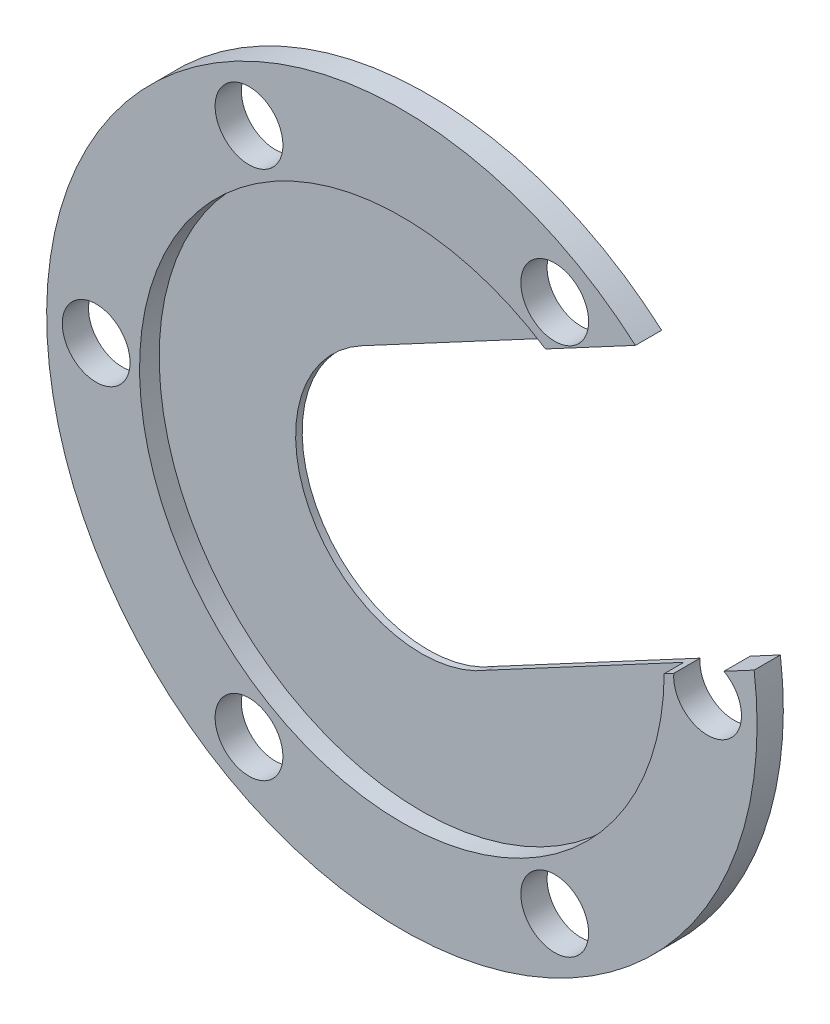
SolidWorks part; units mm, degrees
material "6061 Alloy"
ref_plane "Front Plane" through (0, 0, 0) normal (0, 0, 1) x (1, 0, 0)
ref_plane "Top Plane" through (0, 0, 0) normal (0, 1, 0) x (1, 0, 0)
ref_plane "Right Plane" through (0, 0, 0) normal (1, 0, 0) x (0, 0, -1)
sketch "Sketch2" plane through (0, 0, 0) normal (0, 0, 1) x (1, 0, 0)
  circle A2 centre (0, 0) radius 42.9895
  circle A3 centre (-18.4976, 32.0387) radius 4.1021
  circle A5 centre (18.4976, 32.0387) radius 4.1021
  circle A7 centre (36.9951, 0) radius 4.1021
  circle A9 centre (18.4976, -32.0387) radius 4.1021
  circle A11 centre (-18.4976, -32.0387) radius 4.1021
  circle A13 centre (-36.9951, 0) radius 4.1021
  circle A14 centre (0, 0) radius 15.24
  dimension "D2" = 30.48
extrude "Boss-Extrude2" add sketch "Sketch2" along normal blind 3.175
sketch "Sketch3" plane through (0, 0, 3.175) normal (0, 0, 1) x (1, 0, 0)
  line L0 (-7.1852, 13.4399) -> (37.8444, 37.5134)
  line L1 (6.3071, -13.8737) -> (51.5632, 10.321)
  line L2 (-7.1852, 13.4399) -> (6.3071, -13.8737)
  line L3 (37.8444, 37.5134) -> (51.5632, 10.321)
  circle A0 centre (0, 0) radius 31.75
  circle A1 centre (0, 0) radius 15.24 construction
  dimension "D1" = 63.5
extrude "Cut-Extrude1" cut sketch "Sketch3" against normal blind 2.3813 contours A0
extrude "Cut-Extrude2" cut sketch "Sketch3<3>" against normal blind 4.1275 contours L3 L1 L2 L0
sketch "Sketch3<3>" plane through (0, 0, 3.175) normal (0, 0, 1) x (1, 0, 0) same geometry as "Sketch3"
